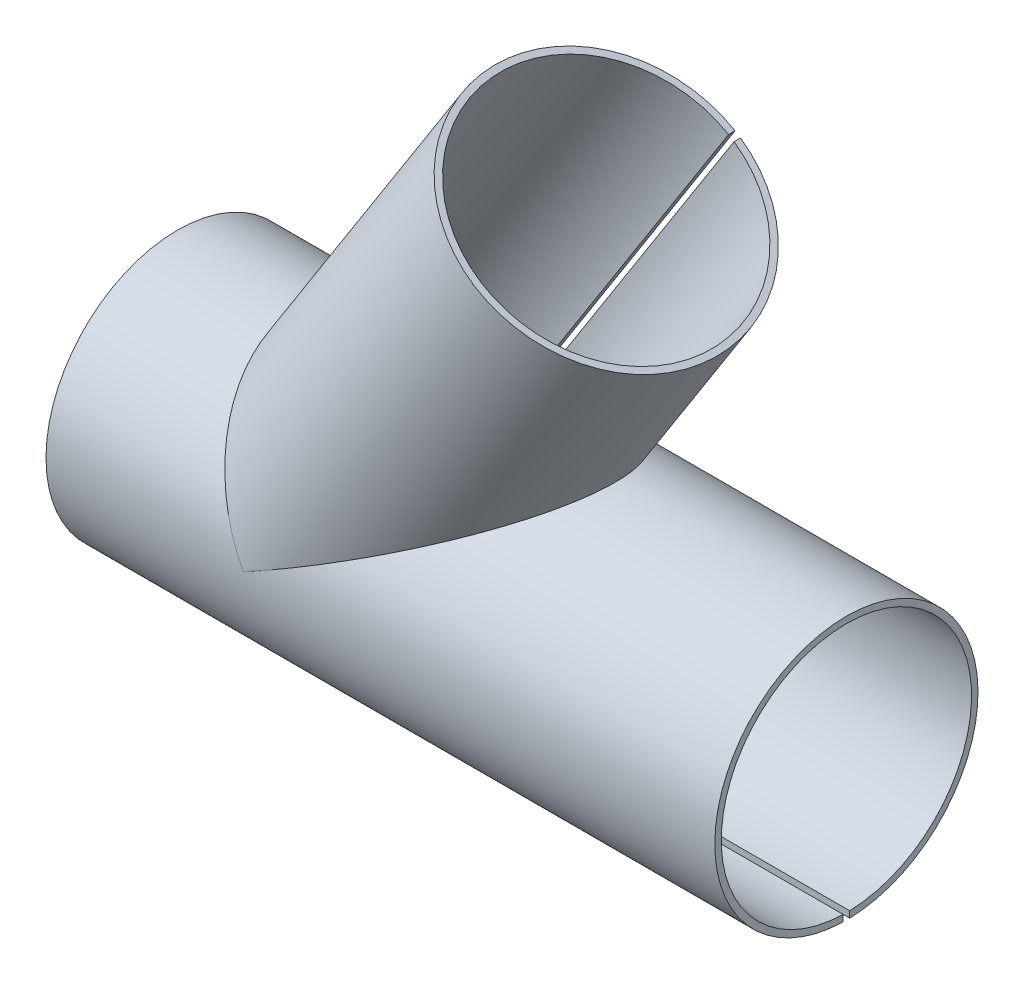
SolidWorks part; units mm, degrees
ref_plane "前视基准面" through (0, 0, 0) normal (0, 0, 1) x (1, 0, 0)
ref_plane "上视基准面" through (0, 0, 0) normal (0, 1, 0) x (1, 0, 0)
ref_plane "右视基准面" through (0, 0, 0) normal (1, 0, 0) x (0, 0, -1)
sketch "草图1" plane through (0, 0, 0) normal (0, 0, 1) x (1, 0, 0)
  line L0 (-30.5416, 0) -> (72.9721, 0) construction
  line L1 (0, 0) -> (35.7984, 56.1785) construction
  line L2 (72.9721, 20.3684) -> (72.9721, -20.3684) construction
  line L3 (18.6211, 67.1243) -> (52.9757, 45.2327) construction
  line L4 (52.9757, 45.2327) -> (37.1315, 20.3684) construction
  line L5 (37.1315, 20.3684) -> (72.9721, 20.3684) construction
  line L6 (18.6211, 67.1243) -> (-11.173, 20.3684) construction
  line L7 (-11.173, 20.3684) -> (-30.5416, 20.3684) construction
  line L8 (-30.5416, 20.3684) -> (-30.5416, -20.3684) construction
  line L9 (0, 0) -> (0, -1) construction
  line L10 (-11.173, 20.3684) -> (0, 0) construction
  line L11 (0, 0) -> (37.1315, 20.3684) construction
  line L12 (-11.173, 20.3684) -> (-11.173, 19.3684) construction
  line L13 (0, 0) -> (35.7984, 56.1785)
  dimension "L3" = 103.5137
  dimension "R" = 20.3684
  dimension "L1" = 66.6149
  dimension "L2" = 19.3686
  dimension "B" = 57.494
  dimension "t" = 1
sketch "草图2" plane through (0, 0, 0) normal (1, 0, 0) x (0, 0, -1)
  circle A0 centre (0, 0) radius 20.3684
extrude "拉伸-薄壁1" add sketch "草图2" along normal up to vertex (72.9721 mm away) and the other way up to vertex (30.5416 mm away) thin up to point (72.9721, 0, 0) other way up to point (-30.5416, 0, 0) thin type one direction reverse wall 1
ref_plane "基准面1" through (35.7984, 56.1785, 0) normal (0.5374, 0.8433, 0) x (-0.8433, 0.5374, 0)
sketch "草图3" plane through (35.7984, 56.1785, 0) normal (0.5374, 0.8433, 0) x (-0.8433, 0.5374, 0)
  circle A0 centre (0, 0) radius 20.3684
extrude "拉伸-薄壁2" add sketch "草图3" against normal up to vertex (66.6149 mm away) separate body thin up to point (0, 0, 0) thin type one direction reverse wall 1
sketch "草图4" plane through (0, 0, 0) normal (0, 0, 1) x (1, 0, 0)
  line L0 (-11.173, 20.3684) -> (0, 0)
  line L1 (0, 0) -> (37.1315, 20.3684)
  line L2 (37.1315, 20.3684) -> (-11.173, 20.3684)
extrude "切除-拉伸1" cut sketch "草图4" against normal through all and the other way through all
sketch "草图5" plane through (0, 0, 0) normal (0, 0, 1) x (1, 0, 0)
  line L0 (52.9757, 45.2327) -> (37.1315, 20.3684) construction
  line L1 (18.6211, 67.1243) -> (52.9757, 45.2327) construction
  line L2 (18.6211, 67.1243) -> (-11.173, 20.3684) construction
  line L3 (-11.173, 20.3684) -> (0, 0) construction
  line L4 (0, 0) -> (37.1315, 20.3684) construction
  line L5 (52.9757, 45.2327) -> (37.1315, 20.3684)
  line L6 (18.6211, 67.1243) -> (52.9757, 45.2327)
  line L7 (18.6211, 67.1243) -> (-11.173, 20.3684)
  line L8 (-11.173, 20.3684) -> (0, 0)
  line L9 (0, 0) -> (37.1315, 20.3684)
extrude "切除-拉伸2" cut sketch "草图5" against normal through all and the other way through all flip side to cut
sketch "草图6" plane through (0, 0, 0) normal (0, 1, 0) x (1, 0, 0)
  line L0 (-30.5416, 0) -> (72.9721, 0)
extrude "切除-拉伸-薄壁1" cut sketch "草图6" against normal through all thin thin type mid plane wall 1
extrude "切除-拉伸-薄壁2" cut sketch "草图1" against normal through all thin thin type mid plane wall 1
equation "\"D5@拉伸-薄壁1\" = \"t@草图1\""
equation "\"D5@拉伸-薄壁2\" = \"t@草图1\""
